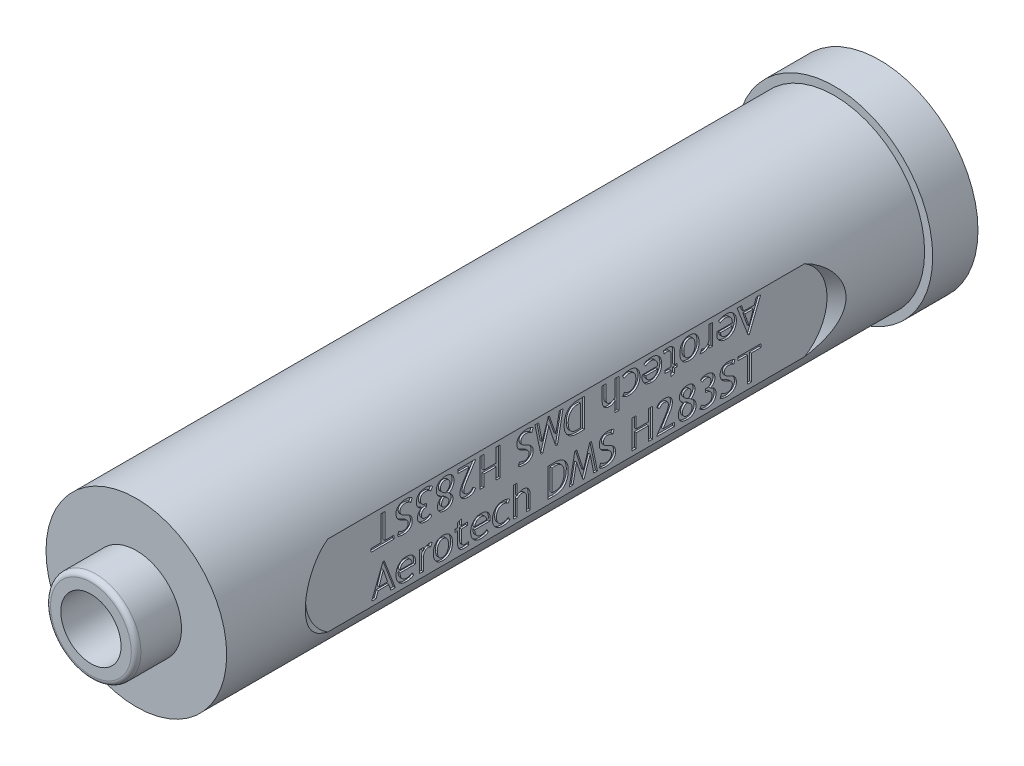
SolidWorks part; units mm, degrees
ref_plane "Front Plane" through (0, 0, 0) normal (0, 0, 1) x (1, 0, 0)
ref_plane "Top Plane" through (0, 0, 0) normal (0, 1, 0) x (1, 0, 0)
ref_plane "Right Plane" through (0, 0, 0) normal (1, 0, 0) x (0, 0, -1)
sketch "Sketch1" plane through (0, 0, 0) normal (0, 0, 1) x (1, 0, 0)
  circle A0 centre (0, 0) radius 19.05
  dimension "D1" = 38.1
extrude "Boss-Extrude1" add sketch "Sketch1" along normal blind 156.718
sketch "Sketch2" plane through (0, 0, 0) normal (0, 0, 1) x (1, 0, 0)
  circle A0 centre (0, 0) radius 20.7518
  dimension "D1" = 41.5036
extrude "Boss-Extrude2" add sketch "Sketch2" along normal blind 9.5504
sketch "Sketch3" plane through (0, 0, 156.718) normal (0, 0, 1) x (1, 0, 0)
  circle A0 centre (0, 0) radius 9.525
  dimension "D1" = 19.05
extrude "Boss-Extrude3" add sketch "Sketch3" along normal blind 9.5758
fillet "Fillet1" radius 1.016 1 edges at (9.525, 0, 166.2938)
sketch "Sketch4" plane through (0, 0, 166.2938) normal (0, 0, 1) x (1, 0, 0)
  circle A0 centre (0, 0) radius 6.35
  dimension "D1" = 12.7
extrude "Cut-Extrude1" cut sketch "Sketch4" against normal blind 18.796
sketch "Sketch5" plane through (0, 0, 0) normal (1, 0, 0) x (0, 0, -1)
  line L0 (-36.0433, 0) -> (-178.1026, 0) construction
  line L1 (0, 0) -> (0, 8.763)
  line L2 (0, 8.763) -> (-14.9301, 4.7625)
  line L3 (-14.9301, 4.7625) -> (-21.3995, 4.7625)
  line L4 (-21.3995, 4.7625) -> (-22.1996, 5.5626)
  line L5 (-22.1996, 5.5626) -> (-123.4694, 5.5626)
  line L6 (-123.4694, 5.5626) -> (-123.4694, 0)
  line L7 (-123.4694, 0) -> (0, 0)
  line L8 (0, -20.7518) -> (0, 20.7518) construction
  line L9 (-22.1996, 5.5626) -> (-24.638, 8.001) construction
  dimension "D1" = 17.526
  dimension "D2" = 9.525
  dimension "D3" = 11.1252
  dimension "D4" = 45
  dimension "D5" = 15
  dimension "D6" = 24.638
  dimension "D7" = 16.002
  dimension "D8" = 123.4694
revolve "Cut-Revolve1" cut sketch "Sketch5" angle 360 about L0
ref_plane "Plane5" through (19.05, 0, 0) normal (1, 0, 0) x (0, 0, -1)
sketch "Sketch18" plane through (19.05, 0, 0) normal (1, 0, 0) x (0, 0, -1)
  line L0 (-128.1342, 0) -> (-38.1342, 0) construction
  line L1 (-128.1342, 12) -> (-38.1342, 12)
  line L2 (-128.1342, -12) -> (-38.1342, -12)
  line L3 (-156.718, 0) -> (-9.5504, 0) construction
  line L4 (-156.718, 19.05) -> (-156.718, -19.05) construction
  line L5 (-9.5504, 19.05) -> (-9.5504, -19.05) construction
  arc A0 (-128.1342, 12) -> (-128.1342, -12) centre (-128.1342, 0) ccw
  arc A1 (-38.1342, -12) -> (-38.1342, 12) centre (-38.1342, 0) ccw
  point P2 (-83.1342, 0)
  point P10 (0, 0)
  point P14 (0, 0)
  point P16 (0, 0)
  point P17 (0, 0)
  dimension "D2" = 90
  dimension "D1" = 24
extrude "Cut-Extrude2" cut sketch "Sketch18" against normal blind 2 draft 45
sketch "Sketch19" plane through (17.05, 0, 0) normal (1, 0, 0) x (0, 0, -1)
  line L0 (-138.1342, 0) -> (-28.1342, 0) construction
  line L1 (-134.7486, -7.5) -> (-31.5198, -7.5) construction
  line L2 (-134.7486, 7.5) -> (-31.5198, 7.5) construction
  line L3 (-83.1342, 7.5) -> (-83.1342, -7.5) construction
  arc A0 (-133.4068, 8.4971) -> (-133.4068, -8.4971) centre (-128.1342, 0) ccw construction
  arc A1 (-32.8616, -8.4971) -> (-32.8616, 8.4971) centre (-38.1342, 0) ccw construction
  text T0 "Aerotech DMS H283ST" font "Trebuchet MS" height 6
  text T1 "Aerotech DMS H283ST" font "Trebuchet MS" height 6
  point P14 (-83.1342, 0)
  dimension "D1" = 15
extrude "Cut-Extrude4" cut sketch "Sketch19" against normal blind 0.4
